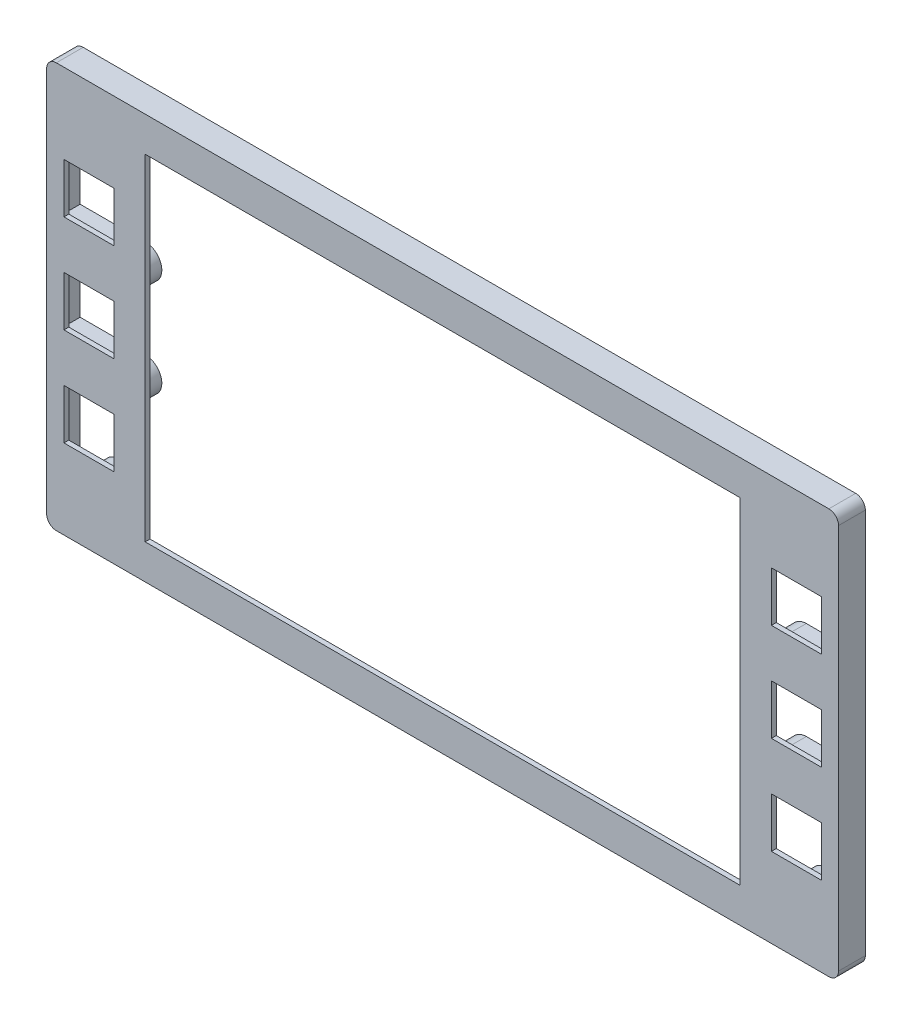
SolidWorks part; units mm, degrees
ref_plane "Front Plane" through (0, 0, 0) normal (0, 0, 1) x (1, 0, 0)
ref_plane "Top Plane" through (0, 0, 0) normal (0, 1, 0) x (1, 0, 0)
ref_plane "Right Plane" through (0, 0, 0) normal (1, 0, 0) x (0, 0, -1)
sketch "PCB" plane through (0, 0, 0) normal (0, 0, 1) x (1, 0, 0)
  line L0 (96.2635, 45.5524) -> (101.8921, 45.5524) construction
  line L1 (-101.8921, 51.181) -> (101.8921, 51.181) construction
  line L2 (-101.8921, 51.181) -> (-101.8921, -51.181) construction
  line L3 (-101.8921, -51.181) -> (101.8921, -51.181) construction
  line L4 (101.8921, 51.181) -> (101.8921, -51.181) construction
  line L5 (-101.8921, 51.181) -> (101.8921, -51.181) construction
  line L6 (-101.8921, -51.181) -> (101.8921, 51.181) construction
  line L7 (96.2635, 45.5524) -> (96.2635, 51.181) construction
  line L8 (-96.2635, 45.5524) -> (-101.8921, 45.5524) construction
  line L9 (-96.2635, -45.5524) -> (-96.2635, -51.181) construction
  line L10 (-92.8243, 0) -> (-92.8243, 25.6794) construction
  line L11 (-98.8568, 31.7119) -> (-86.7918, 31.7119)
  line L12 (-98.8568, 31.7119) -> (-98.8568, 19.6469)
  line L13 (-98.8568, 19.6469) -> (-86.7918, 19.6469)
  line L14 (-86.7918, 31.7119) -> (-86.7918, 19.6469)
  line L15 (-98.8568, 31.7119) -> (-86.7918, 19.6469) construction
  line L16 (-98.8568, 19.6469) -> (-86.7918, 31.7119) construction
  line L17 (-98.8568, 6.0325) -> (-86.7918, 6.0325)
  line L18 (-98.8568, 6.0325) -> (-98.8568, -6.0325)
  line L19 (-98.8568, -6.0325) -> (-86.7918, -6.0325)
  line L20 (-86.7918, 6.0325) -> (-86.7918, -6.0325)
  line L21 (-98.8568, 6.0325) -> (-86.7918, -6.0325) construction
  line L22 (-98.8568, -6.0325) -> (-86.7918, 6.0325) construction
  line L23 (-98.8568, -19.6469) -> (-86.7918, -19.6469)
  line L24 (-98.8568, -19.6469) -> (-98.8568, -31.7119)
  line L25 (-98.8568, -31.7119) -> (-86.7918, -31.7119)
  line L26 (-86.7918, -19.6469) -> (-86.7918, -31.7119)
  line L27 (-98.8568, -19.6469) -> (-86.7918, -31.7119) construction
  line L28 (-98.8568, -31.7119) -> (-86.7918, -19.6469) construction
  line L29 (86.7918, 31.7119) -> (98.8568, 31.7119)
  line L30 (86.7918, 31.7119) -> (86.7918, 19.6469)
  line L31 (86.7918, 19.6469) -> (98.8568, 19.6469)
  line L32 (98.8568, 31.7119) -> (98.8568, 19.6469)
  line L33 (86.7918, 31.7119) -> (98.8568, 19.6469) construction
  line L34 (86.7918, 19.6469) -> (98.8568, 31.7119) construction
  line L35 (86.7918, 6.0325) -> (98.8568, 6.0325)
  line L36 (86.7918, 6.0325) -> (86.7918, -6.0325)
  line L37 (86.7918, -6.0325) -> (98.8568, -6.0325)
  line L38 (98.8568, 6.0325) -> (98.8568, -6.0325)
  line L39 (86.7918, 6.0325) -> (98.8568, -6.0325) construction
  line L40 (86.7918, -6.0325) -> (98.8568, 6.0325) construction
  line L41 (86.7918, -19.6469) -> (98.8568, -19.6469)
  line L42 (86.7918, -19.6469) -> (86.7918, -31.7119)
  line L43 (86.7918, -31.7119) -> (98.8568, -31.7119)
  line L44 (98.8568, -19.6469) -> (98.8568, -31.7119)
  line L45 (86.7918, -19.6469) -> (98.8568, -31.7119) construction
  line L46 (86.7918, -31.7119) -> (98.8568, -19.6469) construction
  line L47 (-92.8243, 0) -> (-92.8243, -25.6794) construction
  line L48 (-92.8243, 25.6794) -> (-101.8921, 25.6794) construction
  line L49 (92.8243, 25.6794) -> (101.8921, 25.6794) construction
  circle A0 centre (-96.2635, 45.5524) radius 0.9995
  circle A1 centre (-96.2635, -45.5524) radius 0.9995
  circle A2 centre (96.2635, -45.5524) radius 0.9995
  circle A3 centre (96.2635, 45.5524) radius 0.9995
  point P0 (0, 0)
  point P14 (-92.8243, 25.6794)
  point P23 (-92.8243, 0)
  point P28 (-92.8243, -25.6794)
  point P33 (92.8243, 25.6794)
  point P38 (92.8243, 0)
  point P43 (92.8243, -25.6794)
  dimension "D4" = 1.999
  dimension "D1" = 203.7842
  dimension "D2" = 102.362
  dimension "D3" = 5.6286
  dimension "D5" = 25.5016
  dimension "D6" = 25.5016
  dimension "D7" = 9.0678
  dimension "D8" = 12.065
sketch "display_screen" plane through (0, 0, 0) normal (0, 0, 1) x (1, 0, 0)
  line L1 (-80.3275, 46.3296) -> (83.7565, 46.3296) construction
  line L2 (-80.3275, 46.3296) -> (-80.3275, -50.9016) construction
  line L3 (-80.3275, -50.9016) -> (83.7565, -50.9016) construction
  line L4 (83.7565, 46.3296) -> (83.7565, -50.9016) construction
  line L5 (-78.2955, 44.2976) -> (78.2955, 44.2976) construction
  line L6 (-78.2955, 44.2976) -> (-78.2955, -44.2976) construction
  line L7 (-78.2955, -44.2976) -> (78.2955, -44.2976) construction
  line L8 (78.2955, 44.2976) -> (78.2955, -44.2976) construction
  point P8 (0, 44.2976)
  point P10 (-78.2955, 0)
  dimension "D1" = 164.084
  dimension "D2" = 97.2312
  dimension "D3" = 6.604
  dimension "D4" = 2.032
  dimension "D5" = 2.032
  dimension "D6" = 5.461
ref_plane "foam_thickness" through (0, 0, 2.9972) normal (0, 0, 1) x (1, 0, 0)
ref_plane "face_of_screen" through (0, 0, 5.7658) normal (0, 0, 1) x (1, 0, 0)
sketch "Sketch1" plane through (0, 0, 0) normal (0, 0, 1) x (1, 0, 0)
  line L0 (-101.8921, 51.181) -> (101.8921, 51.181) construction
  line L1 (-103.8961, 53.1596) -> (103.8961, 53.1596)
  line L2 (-103.8961, 53.1596) -> (-103.8961, -53.1596)
  line L3 (-103.8961, -53.1596) -> (103.8961, -53.1596)
  line L4 (103.8961, 53.1596) -> (103.8961, -53.1596)
  line L5 (45.6565, 49.7078) -> (45.6565, 51.4096)
  line L6 (-80.3275, 46.3296) -> (-80.3275, -50.9016) construction
  line L7 (45.6565, 51.4096) -> (-42.2275, 51.4096)
  line L8 (83.7565, 46.3296) -> (83.7565, -50.9016) construction
  line L9 (-102.1461, 51.4096) -> (-102.1461, 53.1596) construction
  line L10 (-102.1461, 51.4096) -> (-103.8961, 51.4096) construction
  line L11 (102.1461, -51.4096) -> (103.8961, -51.4096) construction
  line L12 (102.1461, -51.4096) -> (102.1461, -53.1596) construction
  line L13 (101.8921, 51.181) -> (101.8921, -51.181) construction
  line L14 (-80.3275, 49.7078) -> (-80.3275, 51.4096)
  line L15 (-80.3275, 51.4096) -> (-102.1461, 51.4096)
  line L16 (-102.1461, 51.4096) -> (-102.1461, 17.1069)
  line L17 (-101.8921, 51.181) -> (-101.8921, -51.181) construction
  line L18 (-102.1461, 17.1069) -> (-84.9757, 17.1069)
  line L19 (-42.2275, 51.4096) -> (-42.2275, 49.7078)
  line L20 (77.4065, 49.7078) -> (77.4065, 51.4096)
  line L21 (-84.9757, 8.5725) -> (-102.1461, 8.5725)
  line L22 (-102.1461, 8.5725) -> (-102.1461, -8.5725)
  line L23 (-102.1461, -8.5725) -> (-84.9757, -8.5725)
  line L24 (77.4065, 51.4096) -> (52.0065, 51.4096)
  line L25 (-84.9757, -17.1069) -> (-102.1461, -17.1069)
  line L26 (-102.1461, -17.1069) -> (-102.1461, -51.4096)
  line L27 (52.0065, 49.7078) -> (52.0065, 51.4096)
  line L28 (-80.3275, -50.9016) -> (83.7565, -50.9016) construction
  line L29 (-101.8921, -51.181) -> (101.8921, -51.181) construction
  line L30 (-48.5775, 49.7078) -> (-48.5775, 51.4096)
  line L31 (-98.8568, 19.6469) -> (-86.7918, 19.6469) construction
  line L32 (-98.8568, 6.0325) -> (-86.7918, 6.0325) construction
  line L33 (-98.8568, -6.0325) -> (-86.7918, -6.0325) construction
  line L34 (-48.5775, 51.4096) -> (-73.9775, 51.4096)
  line L35 (-98.8568, -19.6469) -> (-86.7918, -19.6469) construction
  line L36 (-73.9775, 49.7078) -> (-73.9775, 51.4096)
  line L38 (83.7565, 49.7078) -> (83.7565, 51.4096)
  line L39 (83.7565, 51.4096) -> (102.1461, 51.4096)
  line L40 (102.1461, 51.4096) -> (102.1461, 17.1069)
  line L41 (-80.3275, 46.3296) -> (83.7565, 46.3296) construction
  line L42 (102.1461, 17.1069) -> (88.4047, 17.1069)
  line L43 (88.4047, 8.5725) -> (102.1461, 8.5725)
  line L44 (102.1461, 8.5725) -> (102.1461, -8.5725)
  line L45 (102.1461, -8.5725) -> (88.4047, -8.5725)
  line L46 (88.4047, -17.1069) -> (102.1461, -17.1069)
  line L47 (102.1461, -17.1069) -> (102.1461, -51.4096)
  line L48 (102.1461, -51.4096) -> (81.9389, -51.4096)
  line L49 (83.7565, 51.4096) -> (77.4065, 51.4096) construction
  line L50 (52.0065, 51.4096) -> (45.6565, 51.4096) construction
  line L51 (-80.3275, 51.4096) -> (-73.9775, 51.4096) construction
  line L52 (-48.5775, 51.4096) -> (-42.2275, 51.4096) construction
  line L53 (-78.5099, -51.4096) -> (-102.1461, -51.4096)
  line L54 (-46.7599, -51.4096) -> (-75.7951, -51.4096)
  line L55 (47.4741, -51.4096) -> (-44.0451, -51.4096)
  line L56 (79.2241, -51.4096) -> (50.1889, -51.4096)
  arc A0 (88.4047, -8.5725) -> (88.4047, -17.1069) centre (88.4047, -12.8397) ccw
  arc A1 (88.4047, 17.1069) -> (88.4047, 8.5725) centre (88.4047, 12.8397) ccw
  arc A2 (-84.9757, -17.1069) -> (-84.9757, -8.5725) centre (-84.9757, -12.8397) ccw
  arc A3 (-84.9757, 8.5725) -> (-84.9757, 17.1069) centre (-84.9757, 12.8397) ccw
  arc A4 (83.7565, 49.7078) -> (77.4065, 49.7078) centre (80.5815, 49.7078) cw
  arc A5 (52.0065, 49.7078) -> (45.6565, 49.7078) centre (48.8315, 49.7078) cw
  arc A6 (-80.3275, 49.7078) -> (-73.9775, 49.7078) centre (-77.1525, 49.7078) ccw
  arc A7 (-48.5775, 49.7078) -> (-42.2275, 49.7078) centre (-45.4025, 49.7078) ccw
  arc A8 (81.9389, -51.4096) -> (79.2241, -51.4096) centre (80.5815, -54.2798) ccw
  arc A9 (50.1889, -51.4096) -> (47.4741, -51.4096) centre (48.8315, -54.2798) ccw
  arc A10 (-78.5099, -51.4096) -> (-75.7951, -51.4096) centre (-77.1525, -54.2798) cw
  arc A11 (-46.7599, -51.4096) -> (-44.0451, -51.4096) centre (-45.4025, -54.2798) cw
  point P52 (84.1375, 12.8397)
  point P61 (-80.7085, 12.8397)
  point P72 (80.5815, 46.5328)
  point P80 (80.5815, -51.1048)
  point P92 (48.8315, -51.1048)
  point P93 (-77.1525, -51.1048)
  point P94 (-45.4025, -51.1048)
  dimension "D2" = 2.54
  dimension "D3" = 2.54
  dimension "D4" = 2.54
  dimension "D5" = 2.54
  dimension "D6" = 0.2286
  dimension "D7" = 0.254
  dimension "D8" = 0.2286
  dimension "D9" = 0.254
  dimension "D10" = 0.381
  dimension "D11" = 0.381
  dimension "D12" = 0.2032
  dimension "D13" = 6.35
  dimension "D14" = 25.4
  dimension "D15" = 0.2032
  dimension "D16" = 1.75
extrude "Boss-Extrude1" add sketch "Sketch1" along normal up to surface (5.7658 mm away) up to plane "face_of_screen"
sketch "Sketch2" plane through (0, 0, 5.7658) normal (0, 0, 1) x (1, 0, 0)
  line L0 (-78.0415, 44.0436) -> (-78.0415, 44.2976) construction
  line L1 (-103.8961, 53.1596) -> (103.8961, 53.1596)
  line L2 (-103.8961, 53.1596) -> (-103.8961, -53.1596)
  line L3 (-103.8961, -53.1596) -> (103.8961, -53.1596)
  line L4 (103.8961, 53.1596) -> (103.8961, -53.1596)
  line L5 (86.7918, 19.6469) -> (98.8568, 31.7119) construction
  line L6 (99.3648, 32.2199) -> (86.2838, 32.2199)
  line L7 (99.3648, 32.2199) -> (99.3648, 19.1389)
  line L8 (99.3648, 19.1389) -> (86.2838, 19.1389)
  line L9 (86.2838, 32.2199) -> (86.2838, 19.1389)
  line L10 (99.3648, 32.2199) -> (86.2838, 19.1389) construction
  line L11 (99.3648, 19.1389) -> (86.2838, 32.2199) construction
  line L12 (86.7918, 31.7119) -> (98.8568, 31.7119) construction
  line L13 (99.3648, 6.5405) -> (86.2838, 6.5405)
  line L14 (99.3648, 6.5405) -> (99.3648, -6.5405)
  line L15 (99.3648, -6.5405) -> (86.2838, -6.5405)
  line L16 (86.2838, 6.5405) -> (86.2838, -6.5405)
  line L17 (99.3648, 6.5405) -> (86.2838, -6.5405) construction
  line L18 (99.3648, -6.5405) -> (86.2838, 6.5405) construction
  line L19 (99.3648, -19.1389) -> (86.2838, -19.1389)
  line L20 (99.3648, -19.1389) -> (99.3648, -32.2199)
  line L21 (99.3648, -32.2199) -> (86.2838, -32.2199)
  line L22 (86.2838, -19.1389) -> (86.2838, -32.2199)
  line L23 (99.3648, -19.1389) -> (86.2838, -32.2199) construction
  line L24 (99.3648, -32.2199) -> (86.2838, -19.1389) construction
  line L25 (-86.2838, -19.1389) -> (-99.3648, -19.1389)
  line L26 (-86.2838, -19.1389) -> (-86.2838, -32.2199)
  line L27 (-86.2838, -32.2199) -> (-99.3648, -32.2199)
  line L28 (-99.3648, -19.1389) -> (-99.3648, -32.2199)
  line L29 (-78.0415, 44.0436) -> (78.0415, 44.0436)
  line L30 (-78.0415, 44.0436) -> (-78.0415, -44.0436)
  line L31 (-78.0415, -44.0436) -> (78.0415, -44.0436)
  line L32 (78.0415, 44.0436) -> (78.0415, -44.0436)
  line L33 (-78.2955, 44.2976) -> (78.2955, 44.2976) construction
  line L34 (-78.0415, 44.0436) -> (-78.2955, 44.0436) construction
  line L35 (-78.2955, 44.2976) -> (-78.2955, -44.2976) construction
  line L36 (78.0415, -44.0436) -> (78.2955, -44.0436) construction
  line L37 (78.2955, 44.2976) -> (78.2955, -44.2976) construction
  line L38 (78.0415, -44.0436) -> (78.0415, -44.2976) construction
  line L39 (-78.2955, -44.2976) -> (78.2955, -44.2976) construction
  line L40 (-86.2838, -19.1389) -> (-99.3648, -32.2199) construction
  line L41 (-86.2838, -32.2199) -> (-99.3648, -19.1389) construction
  line L42 (-99.3648, 6.5405) -> (-86.2838, 6.5405)
  line L43 (-99.3648, 6.5405) -> (-99.3648, -6.5405)
  line L44 (-99.3648, -6.5405) -> (-86.2838, -6.5405)
  line L45 (-86.2838, 6.5405) -> (-86.2838, -6.5405)
  line L46 (-99.3648, 6.5405) -> (-86.2838, -6.5405) construction
  line L47 (-99.3648, -6.5405) -> (-86.2838, 6.5405) construction
  line L48 (-99.3648, 32.2199) -> (-86.2838, 32.2199)
  line L49 (-99.3648, 32.2199) -> (-99.3648, 19.1389)
  line L50 (-99.3648, 19.1389) -> (-86.2838, 19.1389)
  line L51 (-86.2838, 32.2199) -> (-86.2838, 19.1389)
  line L52 (-99.3648, 32.2199) -> (-86.2838, 19.1389) construction
  line L53 (-99.3648, 19.1389) -> (-86.2838, 32.2199) construction
  point P6 (92.8243, 25.6794)
  point P15 (92.8243, 0)
  point P24 (92.8243, -25.6794)
  point P31 (-92.8243, -25.6794)
  point P38 (-92.8243, 0)
  point P65 (-92.8243, 25.6794)
  dimension "D1" = 0.254
  dimension "D2" = 0.508
extrude "Boss-Extrude2" add sketch "Sketch2" along normal blind 1.27
fillet "Fillet1" radius 2.54 4 edges at (-103.8961, -53.1596, 3.5179) (103.8961, -53.1596, 3.5179) (-103.8961, 53.1596, 3.5179) (103.8961, 53.1596, 3.5179)
sketch "Sketch3" plane through (0, 0, 5.7658) normal (0, 0, -1) x (-1, 0, 0)
  line L0 (-92.825, 38.5525) -> (-92.825, 51.4096) construction
  line L1 (-92.825, 38.5525) -> (92.825, 38.5525) construction
  line L2 (-92.825, 38.5525) -> (-92.825, -38.5525) construction
  line L3 (-92.825, -38.5525) -> (92.825, -38.5525) construction
  line L4 (92.825, 38.5525) -> (92.825, -38.5525) construction
  line L5 (-102.1461, 51.4096) -> (-83.7565, 51.4096) construction
  line L6 (-92.825, 38.5525) -> (-102.1461, 38.5525) construction
  line L7 (-102.1461, 17.1069) -> (-102.1461, 51.4096) construction
  line L8 (92.825, -38.5525) -> (102.1461, -38.5525) construction
  line L9 (102.1461, -17.1069) -> (102.1461, -51.4096) construction
  line L10 (92.825, -38.5525) -> (92.825, -51.4096) construction
  line L11 (102.1461, -51.4096) -> (78.5099, -51.4096) construction
  circle A0 centre (-92.825, 38.5525) radius 1.125
  circle A1 centre (-92.825, 38.5525) radius 2.625
  circle A2 centre (92.825, 38.5525) radius 1.125
  circle A3 centre (92.825, 38.5525) radius 2.625
  circle A4 centre (-92.825, -38.5525) radius 1.125
  circle A5 centre (-92.825, -38.5525) radius 2.625
  circle A6 centre (92.825, -38.5525) radius 1.125
  circle A7 centre (92.825, -38.5525) radius 2.625
  dimension "D1" = 2.25
  dimension "D2" = 1.5
  dimension "D3" = 185.65
  dimension "D4" = 77.105
extrude "Boss-Extrude3" add sketch "Sketch3" along normal up to surface (5.7658 mm away) up to face at (0, 0, 0)
fillet "Fillet2" radius 2 4 edges at (95.45, -38.5525, 5.7658) (-90.2, -38.5525, 5.7658) (-90.2, 38.5525, 5.7658) (95.45, 38.5525, 5.7658)
